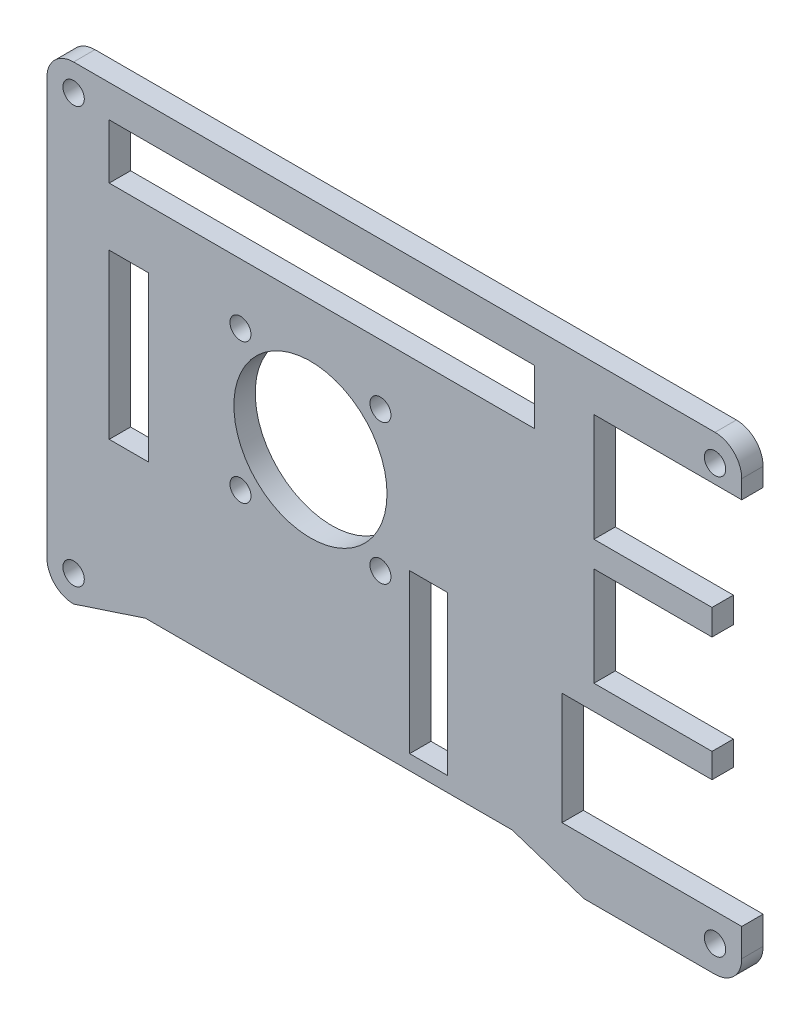
SolidWorks part; units mm, degrees
ref_plane "Front Plane" through (0, 0, 0) normal (0, 0, 1) x (1, 0, 0)
ref_plane "Top Plane" through (0, 0, 0) normal (0, 1, 0) x (1, 0, 0)
ref_plane "Right Plane" through (0, 0, 0) normal (1, 0, 0) x (0, 0, -1)
sketch "Sketch1" plane through (0, 0, 0) normal (0, 0, 1) x (1, 0, 0)
  line L1 (61.2149, 24.0683) -> (61.2149, 26.6839) construction
  line L2 (57.4049, 30.5077) -> (-34.0849, 30.5077) construction
  line L5 (56.975, 4.9979) -> (56.975, 8.6582) construction
  line L9 (56.975, -12.628) -> (56.975, -9.1218) construction
  line L10 (35.575, -12.628) -> (56.975, -12.628) construction
  line L11 (35.575, -28.6278) -> (35.575, -12.628) construction
  line L12 (61.2149, -28.6278) -> (35.575, -28.6278) construction
  line L13 (61.2149, -32.6134) -> (61.2149, -28.6278) construction
  line L14 (38.7143, -36.451) -> (57.405, -36.451) construction
  line L15 (28.4743, -33.0844) -> (38.7143, -36.451) construction
  line L16 (-23.8449, -33.0844) -> (28.4743, -33.0844) construction
  line L17 (-34.0849, -36.451) -> (-23.8449, -33.0844) construction
  line L18 (-37.8949, 26.6977) -> (-37.8949, -32.641) construction
  line L19 (61.2149, 24.0683) -> (40.1348, 24.0683)
  line L20 (61.2149, 24.0683) -> (61.2149, 26.6839)
  line L21 (57.4049, 30.5077) -> (-34.0849, 30.5077)
  line L22 (40.1348, 24.0683) -> (40.1348, 8.6582)
  line L23 (40.1348, 8.6582) -> (56.975, 8.6582)
  line L24 (56.975, 4.9979) -> (56.975, 8.6582)
  line L25 (56.975, 4.9979) -> (40.1348, 4.9979)
  line L26 (40.1348, 4.9979) -> (40.1348, -9.1218)
  line L27 (40.1348, -9.1218) -> (56.975, -9.1218)
  line L28 (56.975, -12.628) -> (56.975, -9.1218)
  line L29 (35.575, -12.628) -> (56.975, -12.628)
  line L30 (35.575, -28.6278) -> (35.575, -12.628)
  line L31 (61.2149, -28.6278) -> (35.575, -28.6278)
  line L32 (61.2149, -32.6134) -> (61.2149, -28.6278)
  line L33 (38.7143, -36.451) -> (57.405, -36.451)
  line L34 (28.4743, -33.0844) -> (38.7143, -36.451)
  line L35 (-23.8449, -33.0844) -> (28.4743, -33.0844)
  line L36 (-34.0849, -36.451) -> (-23.8449, -33.0844)
  line L37 (-37.8949, 26.6977) -> (-37.8949, -32.641)
  line L38 (-23.4169, -23.6989) -> (-23.4169, 9.8012) construction
  line L39 (-29.0049, 25.897) -> (31.6883, 25.897)
  line L40 (-29.0049, 25.897) -> (-29.0049, 18.087)
  line L41 (-29.0049, 18.087) -> (31.6883, 18.087)
  line L42 (31.6883, 25.897) -> (31.6883, 18.087)
  line L43 (-29.0049, 9.8012) -> (-23.4169, 9.8012)
  line L44 (-29.0049, 9.8012) -> (-29.0049, -13.5668)
  line L45 (-29.0049, -13.5668) -> (-23.4169, -13.5668)
  line L46 (-23.4169, 9.8012) -> (-23.4169, -13.5668)
  line L47 (-29.0049, 9.2932) -> (-23.4169, 9.2932)
  line L50 (13.845, -8.3602) -> (19.2484, -8.3602)
  line L51 (13.845, -8.3602) -> (13.845, -30.9668)
  line L52 (13.845, -30.9668) -> (19.2484, -30.9668)
  line L53 (19.2484, -8.3602) -> (19.2484, -30.9668)
  arc A0 (61.2149, 26.6839) -> (57.4049, 30.5077) centre (57.4049, 26.6977) ccw construction
  arc A2 (57.405, -36.451) -> (61.2149, -32.6134) centre (57.405, -32.641) ccw construction
  arc A3 (-37.8949, -32.641) -> (-34.0849, -36.451) centre (-34.0849, -32.641) ccw construction
  arc A4 (-34.0849, 30.5077) -> (-37.8949, 26.6977) centre (-34.0849, 26.6977) ccw construction
  arc A7 (61.2149, 26.6839) -> (57.4049, 30.5077) centre (57.4049, 26.6977) ccw
  circle A8 centre (57.405, -32.641) radius 1.524
  arc A9 (57.405, -36.451) -> (61.2149, -32.6134) centre (57.405, -32.641) ccw
  arc A10 (-37.8949, -32.641) -> (-34.0849, -36.451) centre (-34.0849, -32.641) ccw
  arc A11 (-34.0849, 30.5077) -> (-37.8949, 26.6977) centre (-34.0849, 26.6977) ccw
  circle A12 centre (-34.0849, -32.641) radius 1.524
  circle A13 centre (-34.0849, 26.6977) radius 1.524
  circle A15 centre (57.4049, 26.6977) radius 1.524
  dimension "D5" = 3.048
  dimension "D1" = 23.368
  dimension "D2" = 0.508
  dimension "D3" = 16.8402
  dimension "D4" = 16.8402
extrude "Boss-Extrude1" add sketch "Sketch1" along normal blind 3.048 contours L21 A11 L37 A10 L36 L35 L34 L33 A9 L32 L31 L30 L29 L28 L24 L20 A7 L50 L53 L52 L51 L39 L42 L41 L40 L43 L46 L45 L44 A12 region at (5.2192, -3.5296, 0)
sketch "Sketch2" plane through (0, 0, 3.048) normal (0, 0, 1) x (1, 0, 0)
  line L2 (-37.8949, 26.6977) -> (-37.8949, -32.641) construction
  line L5 (57.4049, 30.5077) -> (-34.0849, 30.5077) construction
  line L6 (-10.2851, -8.9639) -> (-10.2851, 8.0033) construction
  line L7 (-8.7865, -10.4625) -> (8.1807, -10.4625) construction
  line L8 (9.6793, -8.9639) -> (9.6793, 8.0033) construction
  line L9 (8.1807, 9.5019) -> (-8.7865, 9.5019) construction
  line L10 (-10.2851, -10.4625) -> (9.6793, 9.5019) construction
  circle A0 centre (-0.3029, -0.4803) radius 10.922
  circle A1 centre (-10.2851, -10.4625) radius 1.4986
  circle A2 centre (-10.2851, 9.5019) radius 1.4986
  circle A3 centre (9.6793, -10.4625) radius 1.4986
  circle A4 centre (9.6793, 9.5019) radius 1.4986
  dimension "D1" = 26.67
  dimension "D2" = 20.066
  dimension "D3" = 21.844
  dimension "D4" = 16.9672
  dimension "D5" = 2.9972
extrude "Cut-Extrude1" cut sketch "Sketch2" against normal through all
sketch "Sketch3" [suppressed] plane through (0, 0, 3.048) normal (0, 0, 1) x (1, 0, 0)
  line L0 (13.845, -30.9668) -> (19.2484, -30.9668) construction
  line L1 (-29.0049, 25.897) -> (31.6883, 25.897)
  line L2 (-29.0049, 25.897) -> (-29.0049, -30.9668)
  line L3 (-29.0049, -30.9668) -> (31.6883, -30.9668)
  line L4 (31.6883, 25.897) -> (31.6883, -30.9668)
  line L5 (31.6883, 25.897) -> (31.6883, 18.087) construction
extrude "Boss-Extrude2" [suppressed] add sketch "Sketch3" against normal up to vertex up to point (-29.0049, 25.897, 0)
sketch "Sketch4" plane through (0, 0, 3.048) normal (0, 0, 1) x (1, 0, 0)
  circle A0 centre (-34.0849, -32.641) radius 1.524
  circle A1 centre (57.405, -32.641) radius 1.524
  circle A2 centre (-34.0849, -32.641) radius 1.524
  circle A3 centre (-34.0849, 26.6977) radius 1.524
  circle A4 centre (57.4049, 26.6977) radius 1.524
  dimension "D1" = 3.048
extrude "Cut-Extrude2" [suppressed] cut sketch "Sketch4" against normal through all
